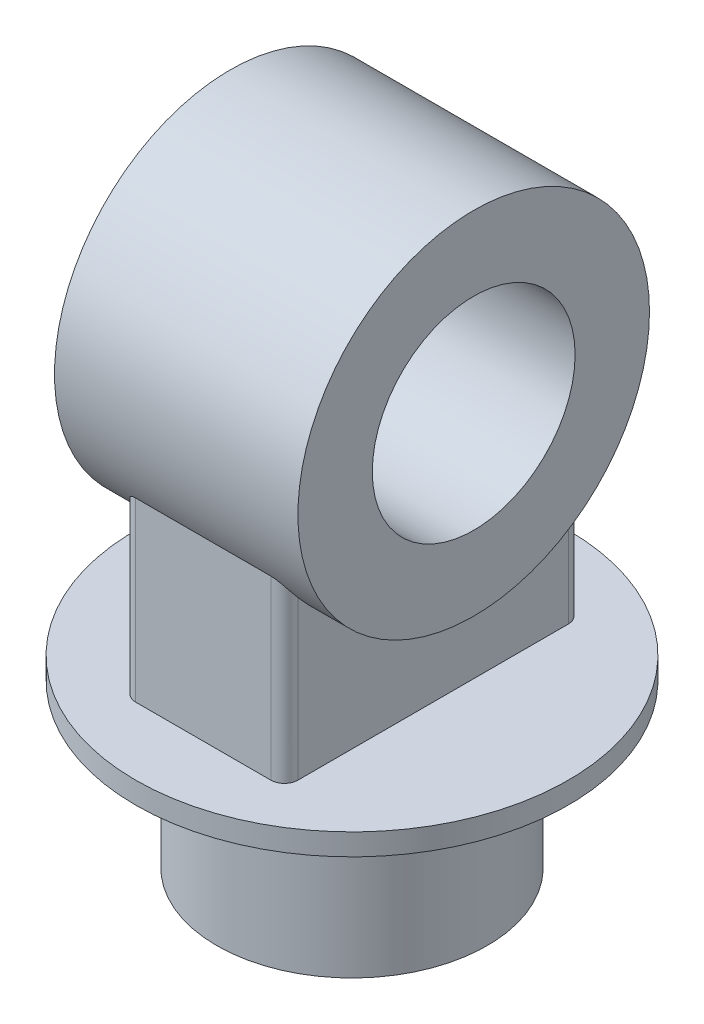
SolidWorks part; units mm, degrees
ref_plane "Front Plane" through (0, 0, 0) normal (0, 0, 1) x (1, 0, 0)
ref_plane "Top Plane" through (0, 0, 0) normal (0, 1, 0) x (1, 0, 0)
ref_plane "Right Plane" through (0, 0, 0) normal (1, 0, 0) x (0, 0, -1)
sketch "Sketch1" plane through (0, 0, 0) normal (0, 1, 0) x (1, 0, 0)
  circle A0 centre (0, 0) radius 1000
extrude "Boss-Extrude1" add sketch "Sketch1" along normal blind 1200
sketch "Sketch2" plane through (0, 1200, 0) normal (0, 1, 0) x (1, 0, 0)
  circle A0 centre (0, 0) radius 1600
  dimension "D1" = 3200
extrude "Boss-Extrude2" add sketch "Sketch2" along normal blind 160
sketch "Sketch3" plane through (0, 0, 0) normal (1, 0, 0) x (0, 0, -1)
  line L0 (1600, 1360) -> (-1600, 1360) construction
  circle A0 centre (0, 3360) radius 750
  circle A1 centre (0, 3360) radius 1300
  dimension "D1" = 1500
  dimension "D2" = 2600
  dimension "D3" = 2000
extrude "Boss-Extrude3" add sketch "Sketch3" along normal mid plane 1800 separate body
sketch "Sketch4" plane through (0, 1360, 0) normal (0, 1, 0) x (1, 0, 0)
  line L1 (600, -1100) -> (-600, -1100)
  line L2 (600, -1100) -> (600, 1100)
  line L3 (600, 1100) -> (-600, 1100)
  line L4 (-600, -1100) -> (-600, 1100)
  line L5 (600, -1100) -> (-600, 1100) construction
  line L6 (600, 1100) -> (-600, -1100) construction
  point P0 (0, 0)
  dimension "D1" = 2200
  dimension "D2" = 1200
extrude "Boss-Extrude4" add sketch "Sketch4" along normal up to next
fillet "Fillet1" radius 100 4 edges at (-600, 2013.5898, 1100) (600, 2013.5898, 1100) (600, 2013.5898, -1100) (-600, 2013.5898, -1100)
